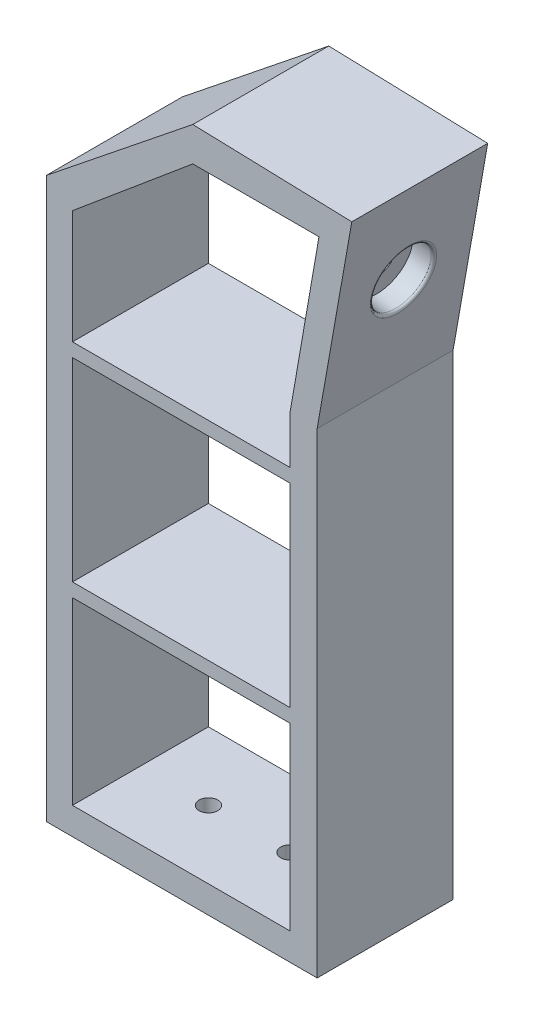
SolidWorks part; units mm, degrees
ref_plane "Front Plane" through (0, 0, 0) normal (0, 0, 1) x (1, 0, 0)
ref_plane "Top Plane" through (0, 0, 0) normal (0, 1, 0) x (1, 0, 0)
ref_plane "Right Plane" through (0, 0, 0) normal (1, 0, 0) x (0, 0, -1)
sketch "Sketch2" plane through (0, 0, 0) normal (0, 0, 1) x (1, 0, 0)
  line L8 (-40.5065, 0) -> (59.131, 0)
  line L10 (59.131, 232.5877) -> (59.801, 236.4462)
  line L12 (59.131, 0) -> (59.131, 175)
  line L14 (59.131, 175) -> (59.131, 265.8716) construction
  line L16 (-40.869, 107.9897) -> (-30.869, 107.9897) construction
  line L17 (65.5005, 211.1233) -> (55.5005, 211.1233) construction
  line L18 (59.131, 87.5) -> (49.131, 87.5) construction
  line L19 (0, 0) -> (0, 10) construction
  line L20 (0, 10) -> (49.131, 10)
  line L21 (49.131, 10) -> (49.131, 87.5)
  line L22 (49.131, 87.5) -> (49.131, 175)
  line L23 (-40.5065, 205.8291) -> (-40.5065, 0)
  line L28 (-30.869, 107.9897) -> (-30.869, 10)
  line L29 (-30.869, 10) -> (0, 10)
  line L30 (59.131, 175) -> (71.87, 247.2467)
  line L32 (-30.869, 107.9897) -> (-30.869, 199.4173)
  line L34 (59.131, 232.5877) -> (49.131, 175)
  line L35 (59.131, 232.5877) -> (68.9791, 230.8512) construction
  line L36 (71.87, 247.2467) -> (13.3973, 249.0046)
  line L37 (13.3973, 249.0046) -> (-40.5065, 205.8291)
  line L38 (42.6337, 248.1256) -> (42.6337, 236.4462) construction
  line L39 (-30.869, 199.4173) -> (6.2516, 230.4687)
  line L40 (59.801, 236.4462) -> (42.6337, 236.4462)
  line L41 (42.6337, 236.4462) -> (13.3973, 236.4462)
  line L44 (13.3973, 249.0046) -> (13.3973, 239.0046) construction
  line L46 (0, 238.2737) -> (6.2516, 230.4687) construction
  line L47 (6.2516, 230.4687) -> (13.3973, 236.4462)
  point P1 (9.131, 107.9897)
  point P2 (0, 0)
  dimension "D1" = 10
  dimension "D2" = 9.131
  dimension "D3" = 49.131
  dimension "D4" = 59.131
  dimension "D5" = 71.87
  dimension "D6" = 30.869
  dimension "D7" = 40.5065
  dimension "D8" = 175
extrude "Boss-Extrude1" add sketch "Sketch2" along normal blind 50
sketch "Sketch10" plane through (0, 10, 0) normal (0, 1, 0) x (1, 0, 0)
  line L0 (49.131, -25) -> (24.131, -25) construction
  line L1 (-30.869, -50) -> (-30.869, 0) construction
  line L3 (-30.869, -25) -> (-5.8513, -25) construction
  line L4 (49.131, -50) -> (49.131, 0) construction
  circle A0 centre (-5.8513, -25) radius 3.425
  circle A1 centre (24.131, -25) radius 3.425
  dimension "D1" = 6.85
  dimension "D2" = 6.85
  dimension "D3" = 25.0177
  dimension "D4" = 55
extrude "Cut-Extrude5" cut sketch "Sketch10" against normal blind 10
sketch "Sketch11" plane through (0, 0, 50) normal (0, 0, 1) x (1, 0, 0)
  line L1 (-30.869, 157.6357) -> (49.131, 157.6357)
  line L2 (49.131, 10) -> (49.131, 175) construction
  line L6 (-30.869, 10) -> (-30.869, 81.1513) construction
  line L7 (-30.869, 81.1513) -> (-30.869, 157.6357) construction
  line L8 (-30.869, 199.4173) -> (-30.869, 10) construction
  line L9 (49.131, 157.6357) -> (49.131, 152.6357)
  line L10 (49.131, 152.6357) -> (-30.869, 152.6357)
  line L11 (-30.869, 152.6357) -> (-30.869, 157.6357)
  line L12 (-30.869, 81.1513) -> (49.131, 81.1513)
  line L13 (49.131, 81.1513) -> (49.131, 76.1513)
  line L14 (49.131, 76.1513) -> (-30.869, 76.1513)
  line L15 (-30.869, 76.1513) -> (-30.869, 81.1513)
  line L17 (-40.5065, 0) -> (59.131, 0) construction
  dimension "D1" = 5
  dimension "D2" = 5
  dimension "D3" = 76.1513
  dimension "D4" = 152.6357
extrude "Boss-Extrude3" add sketch "Sketch11" against normal blind 50
sketch "Sketch14" plane through (27.4212, -4.8351, 0) normal (0.9848, -0.1736, 0) x (0, 0, -1)
  line L0 (-25, 182.6093) -> (-25, 221.6093) construction
  line L1 (-50, 182.6093) -> (0, 182.6093) construction
  circle A0 centre (-25, 221.6093) radius 11.025
  dimension "D1" = 22.05
extrude "Cut-Extrude6" cut sketch "Sketch14" against normal blind 8
sketch "Sketch15" plane through (19.5427, -3.4459, 0) normal (0.9848, -0.1736, 0) x (0, 0, -1)
  line L0 (-25, 232.6343) -> (-25, 210.5843) construction
  circle A0 centre (-25, 221.6093) radius 11.025 construction
  circle A1 centre (-25, 221.6093) radius 4.05
  dimension "D1" = 8.1
extrude "Cut-Extrude7" cut sketch "Sketch15" against normal blind 3
fillet "Fillet1" radius 1 1 edges at (67.8177, 224.265, 25) type face fillet first side face at (59.9393, 225.6542, 25) second side face at (67.8177, 224.265, 25)
